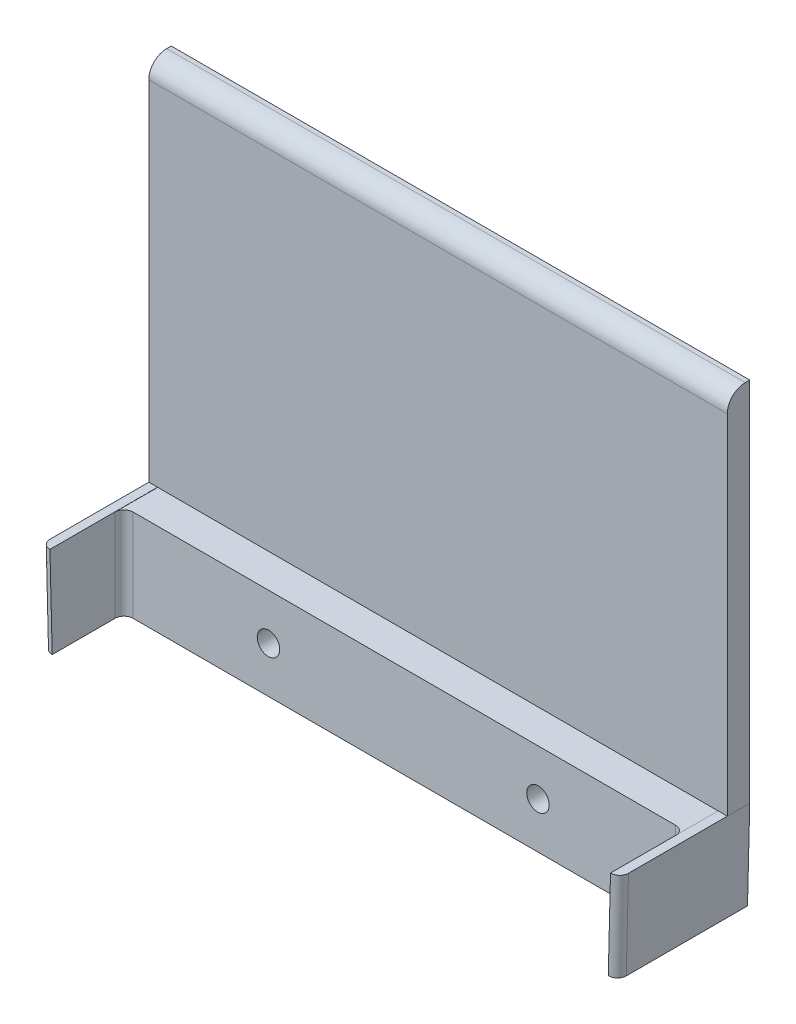
SolidWorks part; units mm, degrees
ref_plane "Front Plane" through (0, 0, 0) normal (0, 0, 1) x (1, 0, 0)
ref_plane "Top Plane" through (0, 0, 0) normal (0, 1, 0) x (1, 0, 0)
ref_plane "Right Plane" through (0, 0, 0) normal (1, 0, 0) x (0, 0, -1)
sketch "Sketch1" plane through (0, 0, 0) normal (0, 0, 1) x (1, 0, 0)
  line L0 (0, -5) -> (0, 5)
  line L1 (31.2, 5) -> (-31.2, 5)
  line L2 (30.95, -5) -> (-30.95, -5)
  line L3 (-31.2, 5) -> (-30.95, -5)
  line L4 (31.2, 5) -> (30.95, -5)
  point P4 (0, 0)
  point P8 (0, 5)
  point P11 (0, -5)
  dimension "D1" = 10
  dimension "D2" = 62.4
  dimension "D3" = 61.9
extrude "Boss-Extrude1" add sketch "Sketch1" along normal blind 4 contours L1 L3 L2 L0 | L4 L1 L0 L2 region at (-15.5376, 0.0067, 0) region at (15.5376, 0.0067, 0)
sketch "Sketch2" plane through (0, 0, 0) normal (1, 0, 0) x (0, 0, -1)
  line L0 (-4, -5) -> (-3.75, 5)
  line L1 (-4, 5) -> (0, 5) construction
  line L2 (-3.75, 5) -> (-4, 5)
  line L3 (-4, 5) -> (-4, -5)
  dimension "D1" = 0.25
extrude "Cut-Extrude1" cut sketch "Sketch2" against normal through all both and the other way through all
sketch "Sketch3" plane through (31.0556, -0.7764, 0) normal (0.9997, -0.025, 0) x (0, 0, -1)
  line L1 (0, -4.2249) -> (-12, -4.2249)
  line L2 (0, -4.2249) -> (0, 5.8016)
  line L3 (0, 5.8016) -> (-12, 5.8016)
  line L4 (-12, -4.2249) -> (-12, 5.8016)
  dimension "D1" = 12
extrude "Boss-Extrude2" add sketch "Sketch3" along normal blind 1
fillet "Fillet1" radius 1 2 edges at (31.075, 0, 3.875) (32.075, -0.0133, 12)
mirror "Mirror1" about plane through (0, 0, 0) normal (1, 0, 0) of bodies 103
sketch "Sketch4" plane through (0, 0, 0) normal (0, 0, -1) x (-1, 0, 0)
  line L0 (-30.95, -5) -> (30.95, -5) construction
  line L1 (-32.2003, 4.9984) -> (32.2003, 4.9984)
  line L2 (-32.2003, 4.9984) -> (-32.2003, 45.8)
  line L3 (-32.2003, 45.8) -> (32.2003, 45.8)
  line L4 (32.2003, 4.9984) -> (32.2003, 45.8)
  line L25 (31.2, 5) -> (-31.2, 5)
  line L26 (-31.2, 5) -> (-31.2006, 5.0234)
  line L27 (-31.2006, 5.0234) -> (-32.2003, 4.9984)
  line L28 (-32.2003, 4.9984) -> (-31.9497, -5.025)
  line L29 (-31.9497, -5.025) -> (-30.95, -5)
  line L30 (-30.95, -5) -> (30.95, -5)
  line L31 (30.95, -5) -> (31.9497, -5.025)
  line L32 (31.9497, -5.025) -> (32.2003, 4.9984)
  line L33 (32.2003, 4.9984) -> (31.2006, 5.0234)
  line L34 (31.2006, 5.0234) -> (31.2, 5)
  line L35 (31.2, 5) -> (-31.2, 5)
  line L36 (-31.2, 5) -> (-31.2006, 5.0234)
  line L37 (-31.2006, 5.0234) -> (-32.2003, 4.9984)
  line L38 (-32.2003, 4.9984) -> (-31.9497, -5.025)
  line L39 (-31.9497, -5.025) -> (-30.95, -5)
  line L40 (-30.95, -5) -> (30.95, -5)
  line L41 (30.95, -5) -> (31.9497, -5.025)
  line L42 (31.9497, -5.025) -> (32.2003, 4.9984)
  line L43 (32.2003, 4.9984) -> (31.2006, 5.0234)
  line L44 (31.2006, 5.0234) -> (31.2, 5)
  line M15 (31.2, 5) -> (-31.2, 5)
  line M16 (-31.2, 5) -> (-31.2006, 5.0234)
  line M17 (-31.2006, 5.0234) -> (-32.2003, 4.9984)
  line M18 (-32.2003, 4.9984) -> (-31.9497, -5.025)
  line M19 (-31.9497, -5.025) -> (-30.95, -5)
  line M20 (-30.95, -5) -> (30.95, -5)
  line M21 (30.95, -5) -> (31.9497, -5.025)
  line M22 (31.9497, -5.025) -> (32.2003, 4.9984)
  line M23 (32.2003, 4.9984) -> (31.2006, 5.0234)
  line M24 (31.2006, 5.0234) -> (31.2, 5)
  dimension "D1" = 50.8
  dimension "D3" = 0
  dimension "D2" = 0
extrude "Boss-Extrude3" add sketch "Sketch4" along normal blind 2.5 contours L4 L3 L2 M23 M17 M16 M15 M24 | L4 L1 M18 M19 M20 M21 M22 M23 region at (0, 25.4002, 0) region at (0, 0.0055, 0)
fillet "Fillet2" radius 2 1 edges at (0, 45.8, 0)
sketch "Sketch9" plane through (0, 0, -2.5) normal (0, 0, -1) x (-1, 0, 0)
  line L0 (7.975, 0) -> (-7.975, 0) construction
  line L1 (0, 7.975) -> (0, -7.975) construction
  point P0 (-15, 0)
  point P1 (15, 0)
  dimension "D1" = 15
  dimension "D2" = 15
hole_wizard "Tap Drill for M3x0.5 Tap3" positions "Sketch10" profile "Sketch11" hole size "M3x0.5" standard "ANSI Metric" end condition through all
sketch "Sketch10" plane through (0, 0, -2.5) normal (0, 0, -1) x (-1, 0, 0)
  point P0 (-15, 0)
  point P3 (15, 0)
sketch "Sketch11" plane through (15, 0, -2.5) normal (1, 0, 0) x (0, 1, 0)
  line L0 (0, 0) -> (0, 14.5)
  line L1 (0, 14.5) -> (1.25, 14.5)
  line L2 (1.25, 14.5) -> (1.25, 0)
  line L5 (1.25, 0) -> (0, 0)
  line L11 (0, -6.35) -> (0, 107.95) construction
  dimension "Thru Hole Dia." = 2.5
  dimension "Thru Hole Depth" = 14.5
